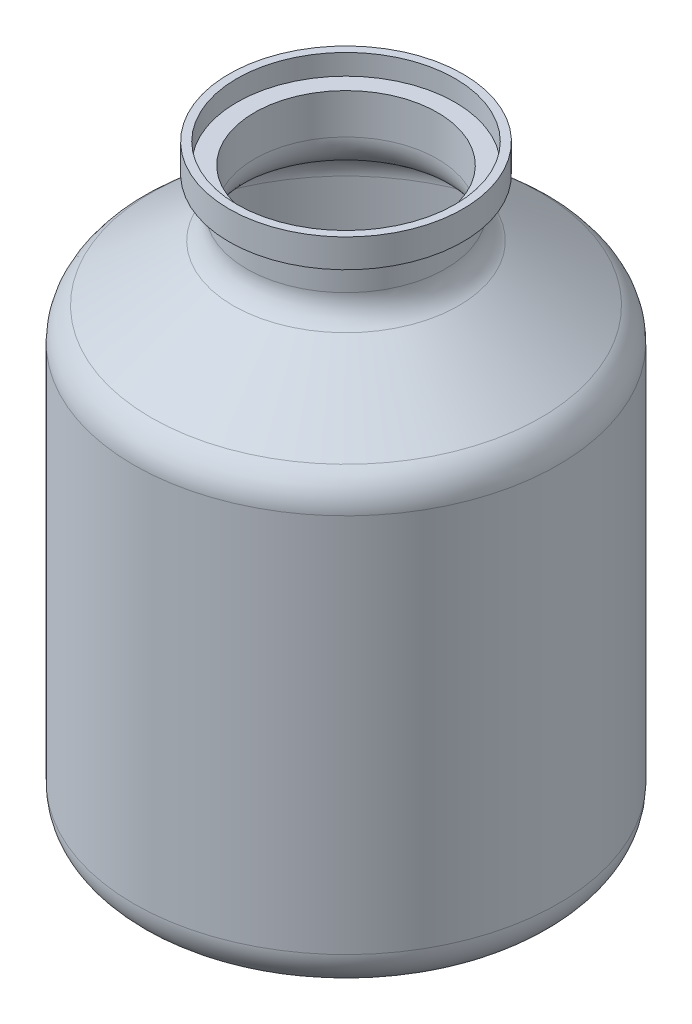
SolidWorks part; units mm, degrees
ref_plane "Front Plane" through (0, 0, 0) normal (0, 0, 1) x (1, 0, 0)
ref_plane "Top Plane" through (0, 0, 0) normal (0, 1, 0) x (1, 0, 0)
ref_plane "Right Plane" through (0, 0, 0) normal (1, 0, 0) x (0, 0, -1)
sketch "Sketch1" plane through (0, 0, 0) normal (0, 0, 1) x (1, 0, 0)
  line L0 (0, 0) -> (55.8506, 0)
  line L1 (68.5506, 12.7) -> (68.5506, 135.5371)
  line L2 (62.9889, 146.0411) -> (36.4262, 164.0924)
  line L3 (32.1096, 172.2449) -> (32.1096, 182.693)
  line L4 (32.1096, 182.693) -> (37.8125, 182.693)
  line L5 (37.8125, 182.693) -> (37.8125, 191.89)
  line L6 (37.8125, 191.89) -> (0, 191.89)
  line L7 (0, 191.89) -> (0, 0)
  arc A0 (55.8506, 0) -> (68.5506, 12.7) centre (55.8506, 12.7) ccw
  arc A1 (68.5506, 135.5371) -> (62.9889, 146.0411) centre (55.8506, 135.5371) ccw
  arc A2 (36.4262, 164.0924) -> (32.1096, 172.2449) centre (41.9665, 172.2449) cw
  point P11 (41.9665, 162.4248)
  point P16 (68.5506, 135.5371)
  dimension "D1" = 12.7
revolve "Revolve1" add sketch "Sketch1" angle 360 about L7
shell "Shell1" thickness 2.54 removed face at (0, 191.89, 37.8125) removed face at (0, 0, 55.8506)
